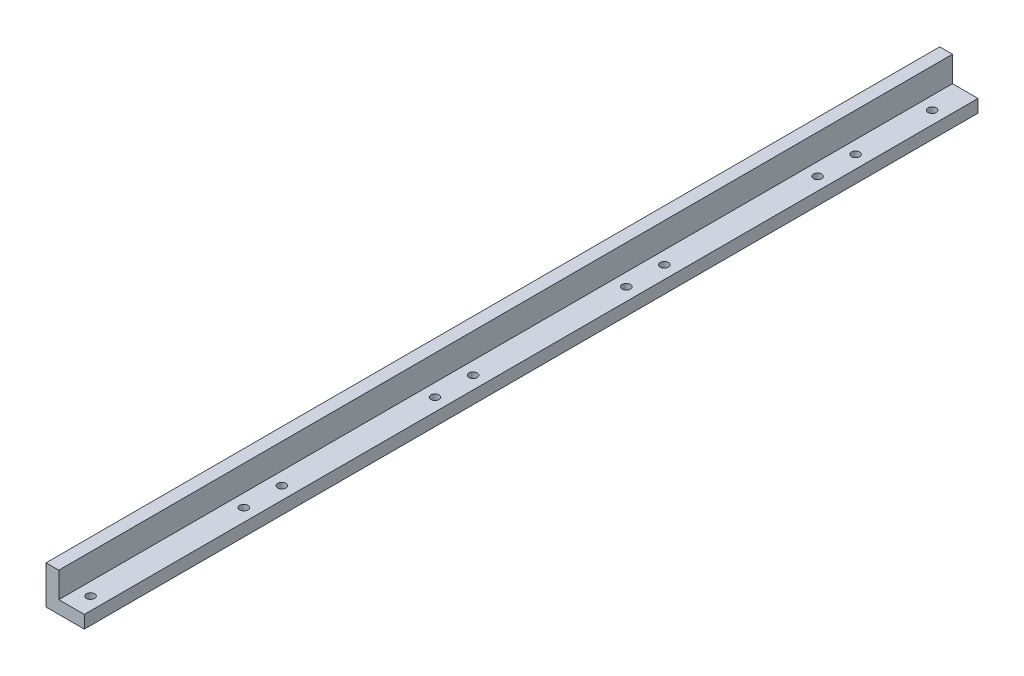
SolidWorks part; units mm, degrees
material "6061 Alloy"
ref_plane "Front Plane" through (0, 0, 0) normal (0, 0, 1) x (1, 0, 0)
ref_plane "Top Plane" through (0, 0, 0) normal (0, 1, 0) x (1, 0, 0)
ref_plane "Right Plane" through (0, 0, 0) normal (1, 0, 0) x (0, 0, -1)
sketch "Sketch1" plane through (0, 0, 0) normal (0, 0, 1) x (1, 0, 0)
  line L0 (0, 0) -> (0, 15)
  line L1 (0, 15) -> (5, 15)
  line L2 (5, 15) -> (5, 5)
  line L3 (5, 5) -> (15, 5)
  line L4 (15, 5) -> (15, 0)
  line L5 (15, 0) -> (0, 0)
  dimension "D1" = 5
  dimension "D2" = 15
  dimension "D3" = 15
extrude "Boss-Extrude1" add sketch "Sketch1" along normal blind 350
hole_wizard "Ø3.2 (3.2) Diameter Hole1" positions "Sketch10" profile "Sketch11" hole size "Ø3.2" standard "ANSI Metric" end condition up to next
sketch "Sketch10" plane through (0, 0, 0) normal (0, -1, 0) x (-1, 0, 0)
  line L0 (0, -350) -> (-15, -350) construction
  line L2 (0, -350) -> (0, 0) construction
  point P0 (-10, -342.55)
  point P2 (-10, -282.55)
  dimension "D1" = 7.45
  dimension "D2" = 60
  dimension "D3" = 10
sketch "Sketch11" plane through (10, 0, 342.55) normal (1, 0, 0) x (0, 0, -1)
  line L0 (0, 0) -> (0, 5)
  line L1 (0, 5) -> (1.6, 5)
  line L2 (1.6, 5) -> (1.6, 0)
  line L5 (1.6, 0) -> (0, 0)
  line L11 (0, -6.35) -> (0, 107.95) construction
  dimension "Thru Hole Dia." = 3.2
  dimension "Thru Hole Depth" = 5
pattern_linear "LPattern2" count 4 spacing 74.9 along (0, 0, -1) of "Ø3.2 (3.2) Diameter Hole1"
hole_wizard "Ø3.2 (3.2) DiameterHoleForAHalfPart" positions "Sketch12" profile "Sketch13" hole size "Ø3.2" standard "ANSI Metric" end condition up to next
sketch "Sketch12" plane through (0, 0, 0) normal (0, -1, 0) x (-1, 0, 0)
  line L0 (-10, -57.85) -> (-10, 7.3574) construction
  circle A0 centre (-10, -57.85) radius 1.6 construction
  point P0 (-10, -42.95)
  point P2 (-10, -12.95)
  dimension "D1" = 30
  dimension "D2" = 14.9
sketch "Sketch13" plane through (10, 0, 42.95) normal (1, 0, 0) x (0, 0, -1)
  line L0 (0, 0) -> (0, 5)
  line L1 (0, 5) -> (1.6, 5)
  line L2 (1.6, 5) -> (1.6, 0)
  line L5 (1.6, 0) -> (0, 0)
  line L11 (0, -6.35) -> (0, 107.95) construction
  dimension "Thru Hole Dia." = 3.2
  dimension "Thru Hole Depth" = 5
